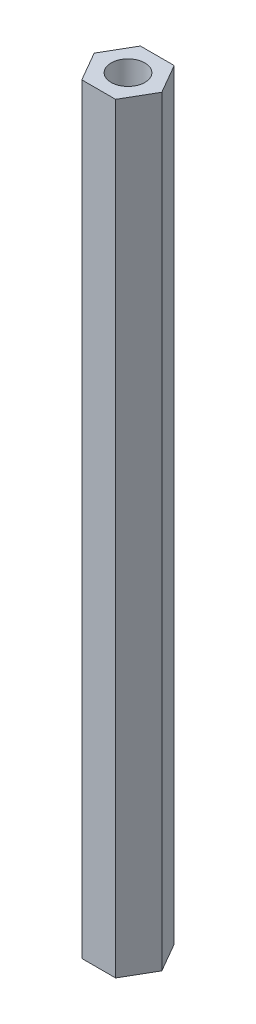
SolidWorks part; units mm, degrees
ref_plane "前视基准面" through (0, 0, 0) normal (0, 0, 1) x (1, 0, 0)
ref_plane "上视基准面" through (0, 0, 0) normal (0, 1, 0) x (1, 0, 0)
ref_plane "右视基准面" through (0, 0, 0) normal (1, 0, 0) x (0, 0, -1)
sketch "草图1" plane through (0, 0, 0) normal (0, 1, 0) x (1, 0, 0)
  line L0 (-1.9018, 4.3296) -> (2.0982, 4.3296)
  line L1 (2.0982, 4.3296) -> (4.0982, 0.8655)
  line L2 (4.0982, 0.8655) -> (2.0982, -2.5986)
  line L3 (2.0982, -2.5986) -> (-1.9018, -2.5986)
  line L4 (-1.9018, -2.5986) -> (-3.9018, 0.8655)
  line L5 (-3.9018, 0.8655) -> (-1.9018, 4.3296)
  line L6 (-3.9018, 0.8655) -> (4.0982, 0.8655)
  line L7 (-1.9018, 4.3296) -> (2.0982, -2.5986)
  circle A1 centre (0.0982, 0.8655) radius 2
  dimension "D5" = 4
  dimension "D1" = 120
  dimension "D2" = 120
  dimension "D3" = 120
  dimension "D4" = 120
  dimension "D6" = 4
  dimension "D7" = 4
  dimension "D8" = 4
  dimension "D9" = 4
extrude "凸台-拉伸1" add sketch "草图1" along normal blind 90 contours A1 L6 L1 L0 L7 | A1 L7 L5 L6 | A1 L6 L4 L3 L7 | A1 L7 L2 L6 region at (-2.2906, 0, -2.2446) region at (1.2926, 0, -2.9342) region at (-1.0962, 0, 1.2033) region at (2.487, 0, 0.5137)
